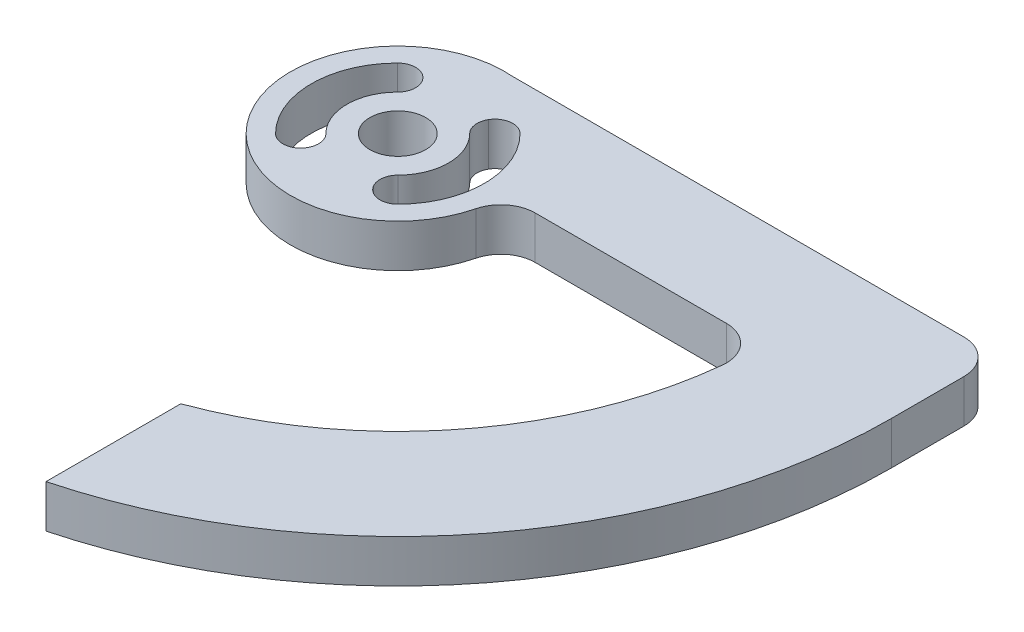
SolidWorks part; units mm, degrees
ref_plane "Front Plane" through (0, 0, 0) normal (0, 0, 1) x (1, 0, 0)
ref_plane "Top Plane" through (0, 0, 0) normal (0, 1, 0) x (1, 0, 0)
ref_plane "Right Plane" through (0, 0, 0) normal (1, 0, 0) x (0, 0, -1)
sketch "Sketch1" plane through (0, 0, 0) normal (0, 1, 0) x (1, 0, 0)
  circle A0 centre (0, 0) radius 12.5
  dimension "D1" = 25
extrude "Boss-Extrude1" add sketch "Sketch1" along normal blind 5
sketch "Sketch4" plane through (0, 0, 0) normal (0, 1, 0) x (1, 0, 0)
  line L0 (0, 0) -> (50, 0) construction
  line L1 (0, 0) -> (14.6186, -47.8152) construction
  arc A0 (14.6186, -47.8152) -> (50, 0) centre (0, 0) ccw
  point P3 (50.7743, -4.7926)
  point P6 (54.6075, 0)
  point P7 (51, 0)
  point P8 (51.6538, 0)
  dimension "D2" = 73
  dimension "D3" = 50
extrude "Extrude-Thin1" add sketch "Sketch4" along normal blind 5 separate body thin thin type mid plane wall 15
sketch "Sketch6" plane through (0, 0, 0) normal (0, 1, 0) x (1, 0, 0)
  line L1 (57.5, 0) -> (1, 0)
  line L2 (57.5, 0) -> (57.5, 12.4599)
  line L3 (57.5, 12.4599) -> (1, 12.4599)
  line L4 (1, 0) -> (1, 12.4599)
  line L5 (29.25, 12.4599) -> (29.25, 0) construction
  line L6 (57.5, 6.23) -> (1, 6.23) construction
  circle A0 centre (0, 0) radius 12.5 construction
  point P104 (29.25, 6.23)
extrude "Boss-Extrude3" add sketch "Sketch6" along normal up to surface (5 mm away) up to face at (0, 5, 12.5)
sketch "Sketch7" plane through (0, 5, 0) normal (0, 1, 0) x (1, 0, 0)
  circle A0 centre (0, 0) radius 3.25
  dimension "D1" = 6.5
extrude "Cut-Extrude3" cut sketch "Sketch7" against normal through all both and the other way through all
sketch "Sketch8" plane through (0, 5, 0) normal (0, 1, 0) x (1, 0, 0)
  line L0 (0, 0) -> (-12.5, 0) construction
  line L1 (0, 0) -> (-4, -6.9282) construction
  arc A0 (1, 12.4599) -> (12.5, 0) centre (0, 0) ccw construction
  arc A1 (-4, 6.9282) -> (-4, -6.9282) centre (0, 0) ccw
  dimension "D1" = 8
  dimension "D2" = 60
extrude "Cut-Extrude-Thin1" cut sketch "Sketch8" against normal blind 5 and the other way through all thin thin type mid plane wall 4.15
mirror "Mirror2" about plane through (0, 0, 0) normal (1, 0, 0) of "Cut-Extrude-Thin1"
fillet "Fillet1" radius 2.075 8 edges at (2.9625, 2.5, -5.1312) (5.0375, 2.5, -8.7252) (-5.0375, 2.5, -8.7252) (-2.9625, 2.5, -5.1312) (2.9625, 2.5, 5.1312) (5.0375, 2.5, 8.7252) (-5.0375, 2.5, 8.7252) (-2.9625, 2.5, 5.1312)
fillet "Fillet2" radius 4 3 edges at (12.5, 2.5, 0) (57.5, 2.5, -12.4599) (42.5, 2.5, 0)
sketch "Sketch9" plane through (0, 0, 0) normal (0, 1, 0) x (1, 0, 0)
  line L0 (16.8114, -54.9875) -> (12.4258, -40.643) construction
  line L1 (0, 0) -> (23.9434, 0) construction
  line L2 (16.0078, 0) -> (38.2916, 0) construction
  line L3 (14.6186, 0) -> (14.6186, -61.8648) construction
  line L4 (12.4258, -40.643) -> (11.863, -56.263)
  line L5 (14.6186, -37.5897) -> (4.9921, -37.5897)
  line L6 (14.6186, -37.5897) -> (14.6186, -60.7122)
  line L7 (14.6186, -60.7122) -> (4.9921, -60.7122)
  line L8 (4.9921, -37.5897) -> (4.9921, -60.7122)
  line L9 (9.8053, -60.7122) -> (9.8053, -37.5897) construction
  line L10 (14.6186, -49.151) -> (4.9921, -49.151) construction
  line L11 (16.8114, -54.9875) -> (12.4258, -40.643)
  arc A0 (16.8114, -54.9875) -> (11.863, -56.263) centre (0, 0) cw
  point P0 (14.6186, -47.8152)
  point P166 (9.8053, -49.151)
extrude "Boss-Extrude4" add sketch "Sketch9" along normal blind 5 contours A0 L11 L6 | A0 L6 L11 L4 region at (13.2318, 0, 50.04) region at (15.3502, 0, 52.8095)
extrude "Cut-Extrude5" cut sketch "Sketch9<4>" along normal through all contours L6 L7 L8 L5
sketch "Sketch9<4>" plane through (0, 0, 0) normal (0, 1, 0) x (1, 0, 0) same geometry as "Sketch9"
